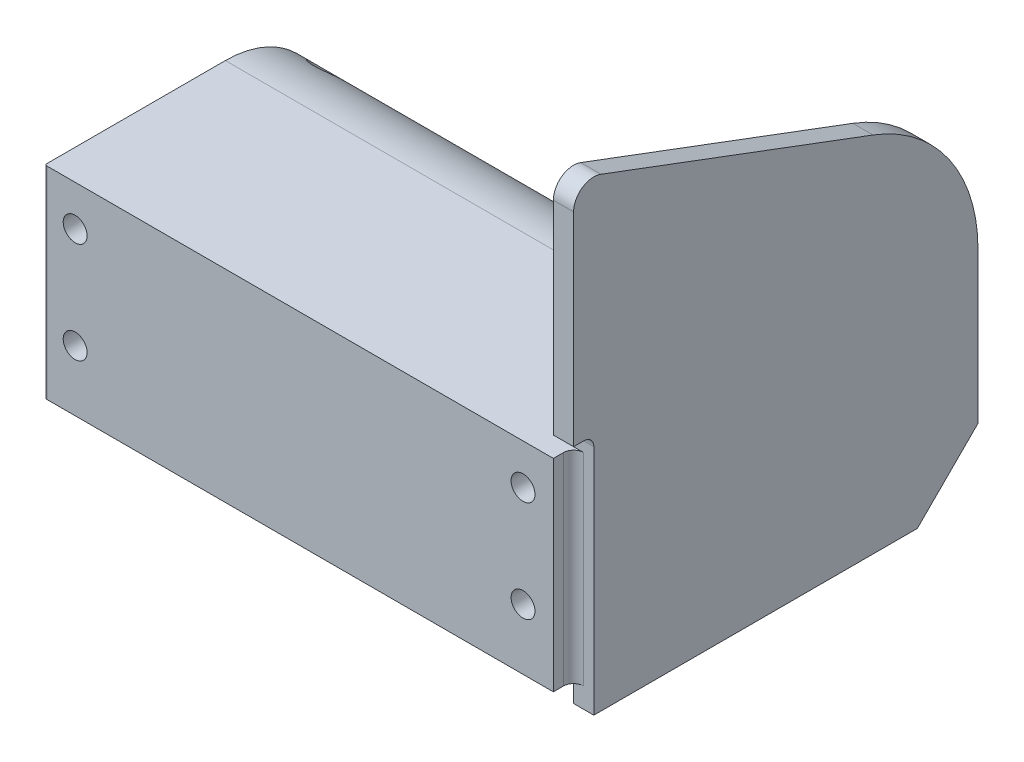
SolidWorks part; units mm, degrees
ref_plane "Front Plane" through (0, 0, 0) normal (0, 0, 1) x (1, 0, 0)
ref_plane "Top Plane" through (0, 0, 0) normal (0, 1, 0) x (1, 0, 0)
ref_plane "Right Plane" through (0, 0, 0) normal (1, 0, 0) x (0, 0, -1)
sketch "Sketch1" plane through (0, 0, 0) normal (0, 0, 1) x (1, 0, 0)
  line L9 (-25.4, 26.67) -> (38.481, 26.67)
  line L11 (-25.4, 26.67) -> (-25.4, 1.27)
  line L12 (38.481, 26.67) -> (38.481, 1.27)
  line L13 (-25.4, 1.27) -> (38.481, 1.27)
  line L18 (6.5405, 26.67) -> (6.5405, 27.2166)
  circle A0 centre (-21.59, 21.59) radius 1.5
  circle A1 centre (-21.59, 8.89) radius 1.5
  circle A2 centre (-21.59, 21.59) radius 2.77
  circle A3 centre (-21.59, 8.89) radius 2.77
  circle A4 centre (34.671, 8.89) radius 1.5
  circle A5 centre (34.671, 8.89) radius 2.77
  circle A6 centre (34.671, 21.59) radius 1.5
  circle A7 centre (34.671, 21.59) radius 2.77
  dimension "D1" = 3
  dimension "D4" = 3
  dimension "D2" = 5.08
  dimension "D3" = 3.81
  dimension "D5" = 3.81
  dimension "D6" = 17.78
  dimension "D7" = 1.27
extrude "Boss-Extrude1" add sketch "Sketch1" along normal blind 2.54 contours L11 L13 L12 L9 A3 A2 A5 A7 | A7 A6 | A5 A4 | A2 A0 | A3 A1 region at (6.5405, 13.8898, 0) region at (-24.2817, 21.59, 0) region at (-24.2817, 8.89, 0) region at (31.9793, 8.89, 0) region at (31.9793, 21.59, 0)
extrude "Boss-Extrude2" add sketch "Sketch1<3>" against normal blind 59.69 contours L11 L13 L12 L9 A3 A2 A5 A7 region at (6.5405, 13.8898, 0)
sketch "Sketch1<3>" plane through (0, 0, 0) normal (0, 0, 1) x (1, 0, 0) same geometry as "Sketch1"
chamfer "Chamfer1" distance 34.29 angle 45 1 edges at (6.5405, 26.67, -59.69)
fillet "Fillet1" radius 12.7 1 edges at (6.5405, 26.67, -25.4)
fillet "Fillet2" radius 1.27 1 edges at (6.5405, 1.27, -50.8)
sketch "Sketch2" plane through (38.481, 0, 0) normal (1, 0, 0) x (0, 0, -1)
  line L7 (40.64, -1.27) -> (48.26, 6.35)
  line L8 (0, -1.27) -> (40.64, -1.27)
  line L9 (0, 29.21) -> (0, -1.27)
  line L10 (-2.54, 29.21) -> (0, 29.21)
  line L11 (-2.54, 54.7548) -> (-2.54, 29.21)
  line L12 (35.0748, 44.3144) -> (0.8919, 57.1331)
  line L13 (48.26, 6.35) -> (48.26, 25.2882)
  line L14 (40.64, -1.27) -> (48.26, 6.35)
  line L16 (0, 29.21) -> (0, -1.27)
  line L17 (-2.54, 29.21) -> (0, 29.21)
  line L18 (-2.54, 54.7548) -> (-2.54, 29.21)
  line L19 (35.0748, 44.3144) -> (0.8919, 57.1331)
  line L20 (48.26, 6.35) -> (48.26, 25.2882)
  line L35 (0, -1.27) -> (40.64, -1.27)
  arc A2 (0.8919, 57.1331) -> (-2.54, 54.7548) centre (0, 54.7548) ccw
  arc A3 (48.26, 25.2882) -> (35.0748, 44.3144) centre (27.94, 25.2882) ccw
  arc A4 (0.8919, 57.1331) -> (-2.54, 54.7548) centre (0, 54.7548) ccw
  arc A5 (48.26, 25.2882) -> (35.0748, 44.3144) centre (27.94, 25.2882) ccw
  dimension "D1" = 0
extrude "Boss-Extrude3" add sketch "Sketch2" along normal up to surface (2.54 mm away)
fillet "Fillet3" radius 1.27 2 edges at (39.751, 29.21, 0) (38.481, 13.97, 0)
fillet "Fillet4" radius 1.27 3 edges at (38.481, 14.0151, -38.0549) (38.481, 25.7033, -24.9996) (38.481, 26.67, -10.0697)
fillet "Fillet5" radius 0.254 1 edges at (-25.4, 13.97, 2.54)
